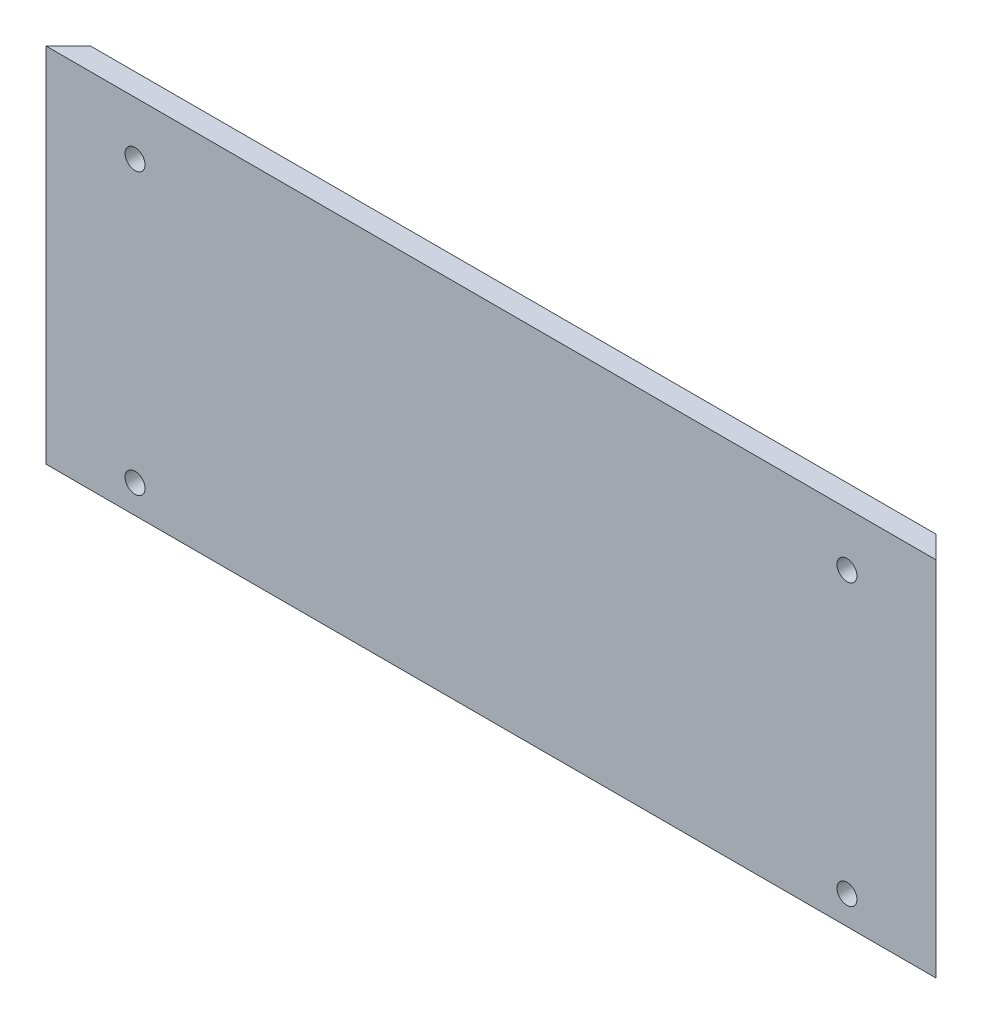
SolidWorks part; units mm, degrees
ref_plane "Front Plane" through (0, 0, 0) normal (0, 0, 1) x (1, 0, 0)
ref_plane "Top Plane" through (0, 0, 0) normal (0, 1, 0) x (1, 0, 0)
ref_plane "Right Plane" through (0, 0, 0) normal (1, 0, 0) x (0, 0, -1)
sketch "Sketch1" plane through (0, 0, 0) normal (0, 0, 1) x (1, 0, 0)
  line L0 (100, 84) -> (100, -37.3998) construction
  line L1 (0, 0) -> (200, 0)
  line L2 (0, 0) -> (0, 84)
  line L3 (0, 84) -> (200, 84)
  line L4 (200, 0) -> (200, 84)
  line L5 (0, 42) -> (200, 42) construction
  circle A0 centre (20, 9) radius 2.25
  circle A1 centre (180, 9) radius 2.25
  circle A4 centre (20, 72) radius 2.25
  circle A5 centre (180, 72) radius 2.25
  dimension "D3" = 20
  dimension "D5" = 4.5
  dimension "D1" = 84
  dimension "D2" = 200
  dimension "D4" = 9
  dimension "D6" = 2
  dimension "D7" = 12
extrude "Boss-Extrude1" add sketch "Sketch1" against normal blind 5
sketch "Sketch2" plane through (0, 0, -5) normal (0, 0, -1) x (-1, 0, 0)
  line L0 (0, 0) -> (-200, 0) construction
  line L1 (0, 0) -> (-200, 0) construction
  line L2 (0, 5) -> (-200, 5)
  line L3 (-200, 5) -> (-200, 84)
  line L4 (-200, 84) -> (0, 84)
  line L5 (0, 84) -> (0, 5)
  circle A1 centre (-20, 9) radius 2.25 construction
  circle A2 centre (-180, 9) radius 2.25 construction
  circle A5 centre (-20, 9) radius 2.25
  circle A6 centre (-180, 9) radius 2.25
  circle A8 centre (-20, 72) radius 2.25 construction
  circle A9 centre (-180, 72) radius 2.25 construction
  circle A10 centre (-20, 72) radius 2.25
  circle A11 centre (-180, 72) radius 2.25
  dimension "D1" = 5
extrude "Boss-Extrude2" add sketch "Sketch2" along normal blind 3
chamfer "Chamfer1" distance 8 angle 45 3 edges at (200, 44.5, -8) (0, 44.5, -8) (100, 84, -8)
chamfer "Chamfer3" distance 3 angle 45 1 edges at (100, 84, -8)
sketch "Sketch3" plane through (100, 0, -100) normal (0.7071, 0, -0.7071) x (-0.7071, 0, -0.7071)
  line L0 (-141.4214, 0) -> (-141.4214, 2.6)
  line L1 (-141.4214, 0) -> (-141.4214, 84) construction
  line L2 (-141.4214, 2.6) -> (-134.3503, 2.6)
  line L4 (-134.3503, 2.6) -> (-134.3503, 0)
  line L5 (-134.3503, 0) -> (-141.4214, 0)
  line L6 (-130.1076, 5) -> (-134.3503, 5) construction
  dimension "D1" = 2.4
extrude "Cut-Extrude1" cut sketch "Sketch3" along direction (1, 0, 0) on the side against the normal through all
